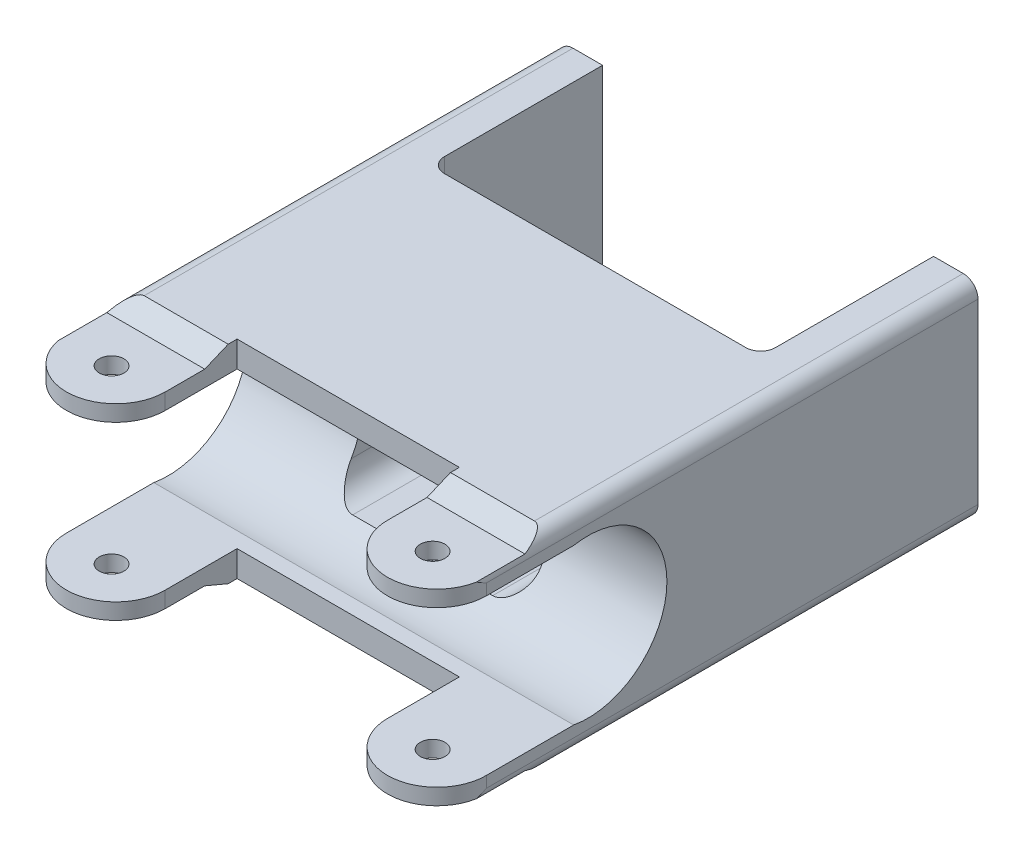
SolidWorks part; units mm, degrees
ref_plane "前视基准面" through (0, 0, 0) normal (0, 0, 1) x (1, 0, 0)
ref_plane "上视基准面" through (0, 0, 0) normal (0, 1, 0) x (1, 0, 0)
ref_plane "右视基准面" through (0, 0, 0) normal (1, 0, 0) x (0, 0, -1)
sketch "Sketch1" plane through (0, 0, 0) normal (0, 1, 0) x (1, 0, 0)
  line L4 (-63.4377, 76.2102) -> (-63.4377, -8.7898)
  line L5 (-63.4377, -8.7898) -> (21.5623, -8.7898)
  line L6 (21.5623, -8.7898) -> (21.5623, 76.2102)
  line L7 (21.5623, 76.2102) -> (-63.4377, 76.2102)
  line L8 (-63.4377, -8.7898) -> (21.5623, -8.7898) construction
  line L9 (-63.4377, -8.7898) -> (-63.4377, -33.7898)
  line L10 (-63.4377, -33.7898) -> (-43.4377, -33.7898)
  line L11 (-43.4377, -33.7898) -> (-43.4377, -8.7898)
  line L12 (21.5623, -8.7898) -> (21.5623, -33.7898)
  line L13 (21.5623, -33.7898) -> (1.5623, -33.7898)
  line L14 (1.5623, -33.7898) -> (1.5623, -8.7898)
  dimension "D1" = 85
  dimension "D2" = 85
  dimension "D3" = 25
  dimension "D4" = 25
  dimension "D5" = 20
  dimension "D6" = 20
extrude "Boss-Extrude1" add sketch "Sketch1" along normal blind 42 contours L6 L7 L4 L5 | L10 L11 L5 L9 | L14 L13 L12 L5 region at (-20.9377, 0, -33.7102) region at (-53.4377, 0, 21.2898) region at (11.5623, 0, 21.2898)
sketch "Sketch2" plane through (0, 42, 0) normal (0, 1, 0) x (1, 0, 0)
  line L0 (-63.4377, 76.2102) -> (-63.4377, -33.7898) construction
  line L1 (-43.4377, -33.7898) -> (-43.4377, -8.7898) construction
  line L2 (-20.9377, -8.7898) -> (-20.9377, -15.3895) construction
  line L3 (-43.4377, -8.7898) -> (1.5623, -8.7898) construction
  line L4 (-63.4377, -23.3345) -> (-63.4377, -33.7898)
  line L5 (-63.4377, -33.7898) -> (-43.4377, -33.7898)
  line L6 (-43.4377, -33.7898) -> (-43.4377, -23.3345)
  line L7 (1.5623, -23.3345) -> (1.5623, -33.7898)
  line L8 (1.5623, -33.7898) -> (21.5623, -33.7898)
  line L9 (21.5623, -33.7898) -> (21.5623, -23.3345)
  arc A0 (-63.4377, -23.3345) -> (-43.4377, -23.3345) centre (-53.4377, -23.3345) ccw
  arc A1 (21.5623, -23.3345) -> (1.5623, -23.3345) centre (11.5623, -23.3345) cw
extrude "Cut-Extrude1" cut sketch "Sketch2" against normal through all
sketch "Sketch3" plane through (-63.4377, 0, 0) normal (-1, 0, 0) x (0, 0, 1)
  line L0 (33.3345, 2) -> (15.3345, 2)
  line L1 (33.3345, 0) -> (33.3345, 42) construction
  line L2 (15.3345, 2) -> (10.5896, 0)
  line L3 (-76.2102, 0) -> (23.3345, 0) construction
  line L4 (33.3345, 21) -> (31.2877, 21) construction
  line L5 (15.3345, 40) -> (10.5896, 42)
  line L6 (33.3345, 40) -> (15.3345, 40)
  line L7 (10.5896, 0) -> (33.3345, 0)
  line L8 (33.3345, 0) -> (33.3345, 2)
  line L9 (10.5896, 42) -> (33.3345, 42)
  line L10 (33.3345, 42) -> (33.3345, 40)
  dimension "D1" = 2
extrude "Cut-Extrude2" cut sketch "Sketch3" against normal through all
sketch "Sketch4" plane through (-63.4377, 0, 0) normal (-1, 0, 0) x (0, 0, 1)
  line L0 (33.3345, 5.2603) -> (5.6433, 5.2603)
  line L1 (33.3345, 2) -> (33.3345, 40) construction
  line L2 (23.3345, 21) -> (11.5107, 21) construction
  line L3 (23.3345, 2) -> (23.3345, 40) construction
  line L4 (33.3345, 36.7397) -> (5.6433, 36.7397)
  line L5 (33.3345, 5.2603) -> (33.3345, 36.7397)
  circle A0 centre (2.7691, 21) radius 16
  point P12 (23.3345, 21)
  line M4 (23.3345, 2) -> (23.3345, 40)
  dimension "D1" = 32
extrude "Cut-Extrude3" cut sketch "Sketch4" against normal through all contours A0 | L2 A0 L0 M4 | L2 L4 A0 M4 | L0 L5 L4 M4 region at (-63.4377, 21, 28.3345) region at (-63.4377, 11.3355, 18.7167) region at (-63.4377, 21, 2.7691) region at (-63.4377, 30.6645, 18.7167)
sketch "Sketch6" plane through (0, 0, -76.2102) normal (0, 0, -1) x (-1, 0, 0)
  line L1 (-21.5623, 42) -> (63.4377, 0) construction
  line L2 (63.4377, 42) -> (-21.5623, 0) construction
  line L3 (-21.5623, 42) -> (63.4377, 42) construction
  line L4 (54.4377, 0) -> (-12.5623, 0)
  line L5 (54.4377, 0) -> (54.4377, 42)
  line L6 (54.4377, 42) -> (-12.5623, 42)
  line L7 (-12.5623, 0) -> (-12.5623, 42)
  line L8 (54.4377, 0) -> (-12.5623, 42) construction
  line L9 (54.4377, 42) -> (-12.5623, 0) construction
  point P8 (20.9377, 21)
  dimension "D1" = 67
extrude "Cut-Extrude4" cut sketch "Sketch6" against normal blind 35
fillet "Fillet1" radius 3 4 edges at (-63.4377, 42, -32.8103) (-63.4377, 0, -32.8103) (21.5623, 42, -32.8103) (21.5623, 0, -32.8103)
fillet "Fillet2" radius 3 2 edges at (12.5623, 21, -41.2102) (-54.4377, 21, -41.2102)
sketch "Sketch9" plane through (0, 0, -41.2102) normal (0, 0, -1) x (-1, 0, 0)
  line L0 (-9.5623, 42) -> (51.4377, 0) construction
  line L1 (51.4377, 0) -> (51.4377, 42) construction
  line L2 (51.4377, 42) -> (-9.5623, 0) construction
  line L4 (35.1033, 7.804) -> (6.7722, 7.804)
  line L5 (40.1033, 12.804) -> (40.1033, 29.196)
  line L6 (35.1033, 34.196) -> (6.7722, 34.196)
  line L7 (1.7722, 12.804) -> (1.7722, 29.196)
  line L8 (40.1033, 7.804) -> (1.7722, 34.196) construction
  line L9 (40.1033, 34.196) -> (1.7722, 7.804) construction
  arc A0 (40.1033, 29.196) -> (35.1033, 34.196) centre (35.1033, 29.196) ccw
  arc A1 (35.1033, 7.804) -> (40.1033, 12.804) centre (35.1033, 12.804) ccw
  arc A2 (6.7722, 7.804) -> (1.7722, 12.804) centre (6.7722, 12.804) cw
  arc A3 (6.7722, 34.196) -> (1.7722, 29.196) centre (6.7722, 29.196) ccw
  point P6 (20.9377, 21)
  dimension "D1" = 5
extrude "Cut-Extrude6" cut sketch "Sketch9" against normal through all both and the other way through all
sketch "Sketch10" plane through (0, 2, 0) normal (0, -1, 0) x (1, 0, 0)
  line L0 (11.4765, 15.3345) -> (11.4765, 22.9079) construction
  line L1 (21.3907, 15.3345) -> (1.5623, 15.3345) construction
  line L2 (-53.3519, 15.3345) -> (-53.3519, 24.0108) construction
  line L3 (-43.4377, 15.3345) -> (-63.2662, 15.3345) construction
  circle A0 centre (11.4765, 22.9079) radius 2.5
  circle A1 centre (-53.3519, 24.0108) radius 2.5
sketch "Sketch11" plane through (0, 0, -76.2102) normal (0, 0, -1) x (-1, 0, 0)
  line L0 (-9.5623, 42) -> (51.4377, 0) construction
  line L1 (-16.5623, 12.5) -> (58.4377, 12.5) construction
  line L2 (-16.5623, 12.5) -> (-16.5623, 29.5) construction
  line L3 (-16.5623, 29.5) -> (58.4377, 29.5) construction
  line L4 (58.4377, 12.5) -> (58.4377, 29.5) construction
  line L5 (-9.5623, 42) -> (51.4377, 42) construction
  line L6 (-9.5623, 42) -> (-9.5623, 0) construction
  line L7 (-9.5623, 0) -> (51.4377, 0) construction
  line L8 (51.4377, 42) -> (51.4377, 0) construction
  line L9 (51.4377, 0) -> (51.4377, 42) construction
  line L10 (51.4377, 42) -> (-9.5623, 0) construction
  line L11 (-21.5623, 25.1731) -> (-16.5623, 25.1731) construction
  line L12 (-21.5623, 39) -> (-21.5623, 3) construction
  line L13 (58.4377, 25.1731) -> (63.4377, 25.1731) construction
  line L14 (63.4377, 39) -> (63.4377, 3) construction
  circle A2 centre (-16.5623, 29.5) radius 2.5
  circle A3 centre (-16.5623, 12.5) radius 2.5
  circle A4 centre (58.4377, 12.5) radius 2.5
  circle A5 centre (58.4377, 29.5) radius 2.5
  point P10 (-16.5623, 21)
  point P11 (-9.5623, 21)
  dimension "D1" = 17
  dimension "D2" = 75
hole_wizard "M5 Tapped Hole2" positions "3DSketch2" profile "Sketch15" tap size "M5" standard "GB"
sketch3d "3DSketch2"
  point P0 (16.5623, 29.5, -76.2102)
  point P3 (16.5623, 12.5, -76.2102)
  point P6 (-58.4377, 12.5, -76.2102)
  point P9 (-58.4377, 29.5, -76.2102)
sketch "Sketch15" plane through (16.5623, 29.5, -76.2102) normal (1, 0, 0) x (0, 1, 0)
  line L0 (0, 0) -> (0, 9.2618)
  line L1 (0, 9.2618) -> (2.1, 8)
  line L2 (2.1, 8) -> (2.1, 0)
  line L5 (2.1, 0) -> (0, 0)
  line L10 (0, 9.2618) -> (-2.1, 8) construction
  line L11 (0, -6.35) -> (0, 107.95) construction
  dimension "Tap Drill Dia." = 4.2
  dimension "Tap Drill Depth" = 8
  dimension "Drill Angle" = 118
cosmetic thread "Hole Thread3" parameters "D1"=8, "D2"=5
cosmetic thread "Hole Thread4" parameters "D1"=8, "D2"=5
cosmetic thread "Hole Thread5" parameters "D1"=8, "D2"=5
cosmetic thread "Hole Thread6" parameters "D1"=8, "D2"=5
sketch "Sketch17" plane through (0, 40, 0) normal (0, 1, 0) x (1, 0, 0)
  line L0 (-53.4377, -33.3345) -> (-53.4377, -6.1345) construction
  line L1 (11.5623, -33.3345) -> (11.5623, -2.2529) construction
  circle A0 centre (-53.4377, -24.2037) radius 2.5
  circle A1 centre (11.5623, -24.2037) radius 2.5
  arc A2 (-63.2662, -25.179) -> (-43.4377, -23.3345) centre (-53.4377, -23.3345) ccw construction
  arc A3 (1.5623, -23.3345) -> (21.3907, -25.179) centre (11.5623, -23.3345) ccw construction
  point P16 (0, 0)
  point P17 (0, 0)
  point P18 (0, 0)
  dimension "D1" = 5
  dimension "D2" = 5
extrude "Cut-Extrude7" cut sketch "Sketch17" against normal through all
